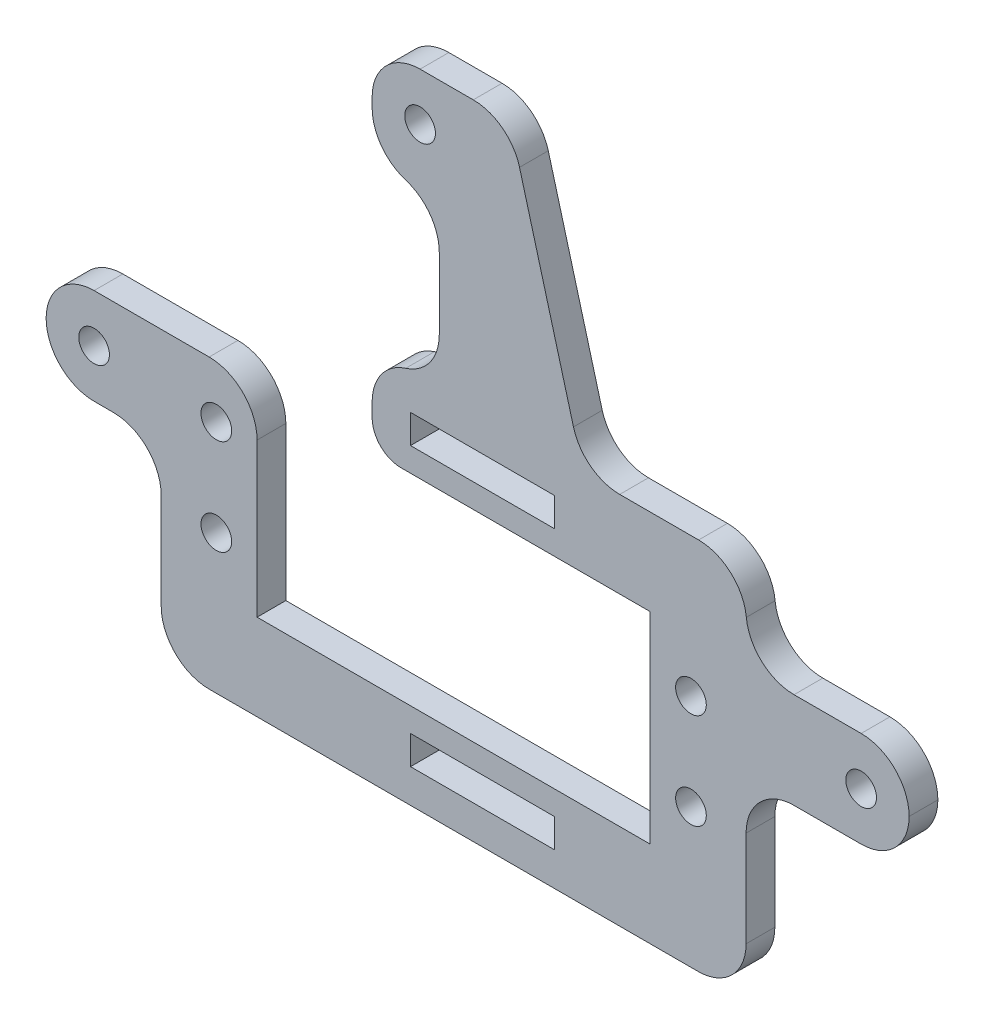
SolidWorks part; units mm, degrees
ref_plane "Plano frontal" through (0, 0, 0) normal (0, 0, 1) x (1, 0, 0)
ref_plane "Plano superior" through (0, 0, 0) normal (0, 1, 0) x (1, 0, 0)
ref_plane "Plano direito" through (0, 0, 0) normal (1, 0, 0) x (0, 0, -1)
sketch "Esboço1" plane through (0, 0, 0) normal (0, 0, 1) x (1, 0, 0)
  line L0 (0, 0) -> (30.5, 0) construction
  line L1 (-30.5, -19.5) -> (30.5, -19.5)
  line L2 (-30.5, -19.5) -> (-30.5, 19.5)
  line L3 (-30.5, 19.5) -> (30.5, 19.5)
  line L4 (30.5, -19.5) -> (30.5, 19.5)
  line L5 (-30.5, -19.5) -> (30.5, 19.5) construction
  line L6 (-30.5, 19.5) -> (30.5, -19.5) construction
  line L7 (-20.5, -10.5) -> (20.5, -10.5)
  line L8 (-20.5, -10.5) -> (-20.5, 10.5)
  line L9 (-20.5, 10.5) -> (20.5, 10.5)
  line L10 (20.5, -10.5) -> (20.5, 10.5)
  line L11 (-20.5, -10.5) -> (20.5, 10.5) construction
  line L12 (-20.5, 10.5) -> (20.5, -10.5) construction
  line L13 (0, 0) -> (0, 19.5) construction
  line L14 (-20.5, 0) -> (-30.5, 0) construction
  line L19 (-4.5, -16) -> (10.5, -16)
  line L25 (10.5, -13) -> (10.5, -16)
  line L34 (-13.75, 44.5) -> (-23.75, 44.5) construction
  line L35 (-13.75, 44.5) -> (-13.75, 19.5) construction
  line L36 (-13.75, 19.5) -> (-23.75, 19.5) construction
  line L37 (-23.75, 44.5) -> (-23.75, 19.5) construction
  line L38 (-13.75, 44.5) -> (-23.75, 19.5) construction
  line L39 (-13.75, 19.5) -> (-23.75, 44.5) construction
  line L40 (-4.5, 13) -> (10.5, 13)
  line L41 (-4.5, 13) -> (-4.5, 16)
  line L42 (-4.5, 16) -> (10.5, 16)
  line L43 (10.5, 13) -> (10.5, 16)
  line L44 (-4.5, 13) -> (10.5, 16) construction
  line L45 (-4.5, 16) -> (10.5, 13) construction
  line L46 (-4.5, -13) -> (10.5, -13)
  line L47 (-4.5, -13) -> (-4.5, -16)
  line L48 (-42.5, 10.5) -> (-30.5, 10.5)
  line L49 (-42.5, 0.5) -> (-30.5, 0.5)
  line L52 (-30.5, 0.5) -> (-30.5, 19.5)
  line L53 (-8.5, 36.5) -> (-8.5, 47.5)
  line L54 (-8.5, 47.5) -> (13.5, 47.5)
  line L55 (47.5, 10.5) -> (47.5, 0.5)
  line L56 (47.5, 0.5) -> (30.5, 0.5)
  line L57 (47.5, 10.5) -> (30.5, 10.5)
  line L58 (-42.5, 0.5) -> (-42.5, 10.5)
  line L59 (-30.5, 10.5) -> (-20.5, 10.5)
  line L60 (-8.5, 36.5) -> (-8.5, 10.5)
  line L61 (13.5, 47.5) -> (13.5, 19.5)
  line L62 (-8.5, 36.5) -> (-1.5, 36.5)
  line L63 (-1.5, 36.5) -> (-1.5, 19.5)
  line L64 (5.8659, 47.5) -> (13.5, 19.5)
  circle A5 centre (-18.75, 39.5) radius 1.6 construction
  circle A9 centre (24.75, 5) radius 1.6
  circle A10 centre (24.75, -5) radius 1.6
  circle A11 centre (-24.75, -5) radius 1.6
  circle A12 centre (-24.75, 5) radius 1.6
  circle A13 centre (-18.75, 14.5) radius 1.6 construction
  circle A14 centre (-37.5, 5.5) radius 1.6
  circle A16 centre (42.5, 5.5) radius 1.6
  circle A17 centre (-3.5, 42.5) radius 1.6
  point P0 (0, 0)
  point P6 (0, 0)
  point P13 (3, 14.5)
  point P38 (-28.281, 5.0682)
  point P57 (-18.75, 32)
  dimension "D5" = 3.2
  dimension "D8" = 15
  dimension "D10" = 25
  dimension "D12" = 5
  dimension "D17" = 5
  dimension "D18" = 5
  dimension "D13" = 6
  dimension "D1" = 41
  dimension "D2" = 21
  dimension "D3" = 9
  dimension "D4" = 10
  dimension "D6" = 49.5
  dimension "D7" = 10
  dimension "D9" = 5
  dimension "D11" = 3
  dimension "D14" = 5
  dimension "D15" = 6
  dimension "D16" = 5
  dimension "D19" = 23
  dimension "D20" = 5
  dimension "D21" = 20
  dimension "D22" = 4
  dimension "D23" = 7
  dimension "D24" = 5
  dimension "D25" = 12
  dimension "D26" = 5
  dimension "D27" = 5
  dimension "D28" = 15
  dimension "D29" = 7
  dimension "D30" = 10
extrude "Ressalto-extrusão1" add sketch "Esboço1" along normal blind 3 contours L1 L4 L3 L2 A10 A9 L10 L7 L8 L9 A14 A11 A12 | L2 A13 A5 | L57 L4 L56 A16 | L64 L54 L53 L62 L63 L3 A17 region at (-29.776, -9.5, 0) region at (-36.5, 0.6562, 0) region at (38.8262, 5.5, 0) region at (2.597, 33.7182, 0)
fillet "Filete1" radius 5 15 edges at (30.5, -19.5, 1.5) (-30.5, -19.5, 1.5) (-30.5, 0.5, 1.5) (30.5, 0.5, 1.5) (30.5, 10.5, 1.5) (-42.5, 10.5, 1.5) (47.5, 10.5, 1.5) (47.5, 0.5, 1.5) (-20.5, 10.5, 1.5) (-42.5, 0.5, 1.5) (-8.5, 47.5, 1.5) (13.5, 19.5, 1.5) (5.8659, 47.5, 1.5) (-8.5, 36.5, 1.5) (-1.5, 19.5, 1.5)
fillet "Filete4" radius 5 3 edges at (-1.5, 36.5, 1.5) (-8.5, 19.5, 1.5) (30.5, 19.5, 1.5)
fillet "Filete5" radius 3 1 edges at (-8.5, 10.5, 1.5)
